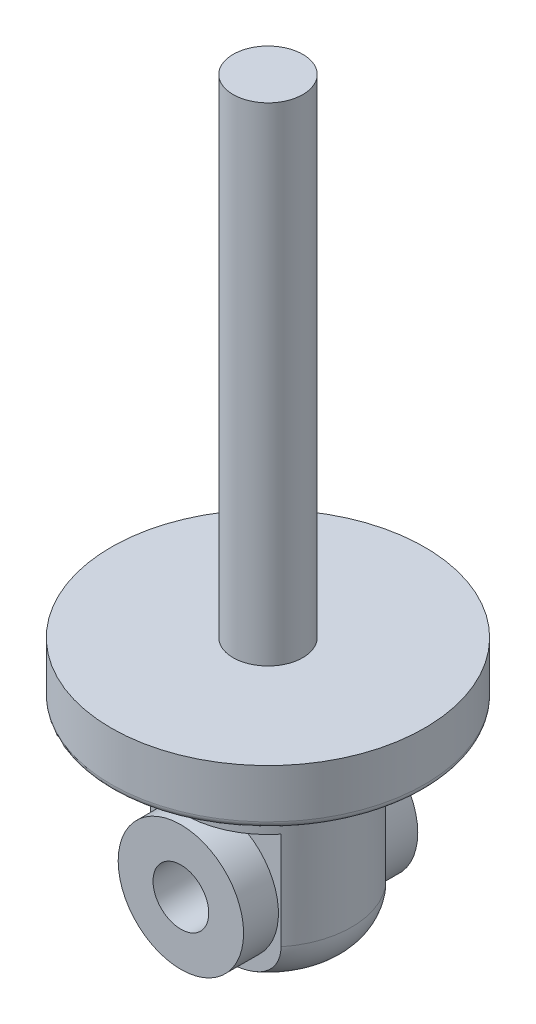
SolidWorks part; units mm, degrees
ref_plane "Front Plane" through (0, 0, 0) normal (0, 0, 1) x (1, 0, 0)
ref_plane "Top Plane" through (0, 0, 0) normal (0, 1, 0) x (1, 0, 0)
ref_plane "Right Plane" through (0, 0, 0) normal (1, 0, 0) x (0, 0, -1)
sketch "Sketch2" plane through (0, 0, 0) normal (0, 1, 0) x (1, 0, 0)
  circle A0 centre (0, 0) radius 22.5
  dimension "D1" = 45
extrude "Boss-Extrude1" add sketch "Sketch2" along normal blind 8
sketch "Sketch3" plane through (0, 8, 0) normal (0, 1, 0) x (1, 0, 0)
  circle A0 centre (0, 0) radius 5
  dimension "D1" = 10
extrude "Boss-Extrude2" add sketch "Sketch3" along normal blind 70
sketch "Sketch4" plane through (0, 0, 0) normal (0, -1, 0) x (1, 0, 0)
  circle A0 centre (0, 0) radius 12
  dimension "D1" = 24
extrude "Boss-Extrude3" add sketch "Sketch4" along normal blind 28
fillet "Fillet1" radius 6 1 edges at (0, -28, -12)
sketch "Sketch5" plane through (0, 0, 0) normal (1, 0, 0) x (0, 0, -1)
  line L0 (0, 0) -> (0, -28) construction
  line L1 (-6, -28) -> (6, -28) construction
  line L2 (7.5, -28) -> (7.5, -8)
  line L7 (-7.5, -28) -> (-22.5, -28)
  line L8 (-7.5, -28) -> (-7.5, -8)
  line L9 (-7.5, -8) -> (-22.5, -8)
  line L10 (-22.5, -28) -> (-22.5, -8)
  line L11 (7.5, -28) -> (22.5, -28)
  line L12 (22.5, -28) -> (22.5, -8)
  line L13 (7.5, -8) -> (22.5, -8)
  dimension "D1" = 20
  dimension "D2" = 15
  dimension "D3" = 15
extrude "Cut-Extrude1" cut sketch "Sketch5" against normal through all both and the other way through all
sketch "Sketch6" plane through (0, 0, -7.5) normal (0, 0, -1) x (-1, 0, 0)
  line L0 (-6, -28) -> (6, -28) construction
  circle A0 centre (0, -18) radius 4
  dimension "D2" = 8
  dimension "D1" = 10
extrude "Cut-Extrude2" cut sketch "Sketch6" against normal blind 28
sketch "Sketch7" plane through (0, 0, 0) normal (0, 0, 1) x (1, 0, 0)
  circle A0 centre (0, -18) radius 9
  circle A1 centre (0, -18) radius 4 construction
  circle A2 centre (0, -18) radius 4
  dimension "D1" = 18
extrude "Boss-Extrude5" add sketch "Sketch7" along normal mid plane 25
fillet "Fillet3" radius 1 1 edges at (0, 0, 22.5)
